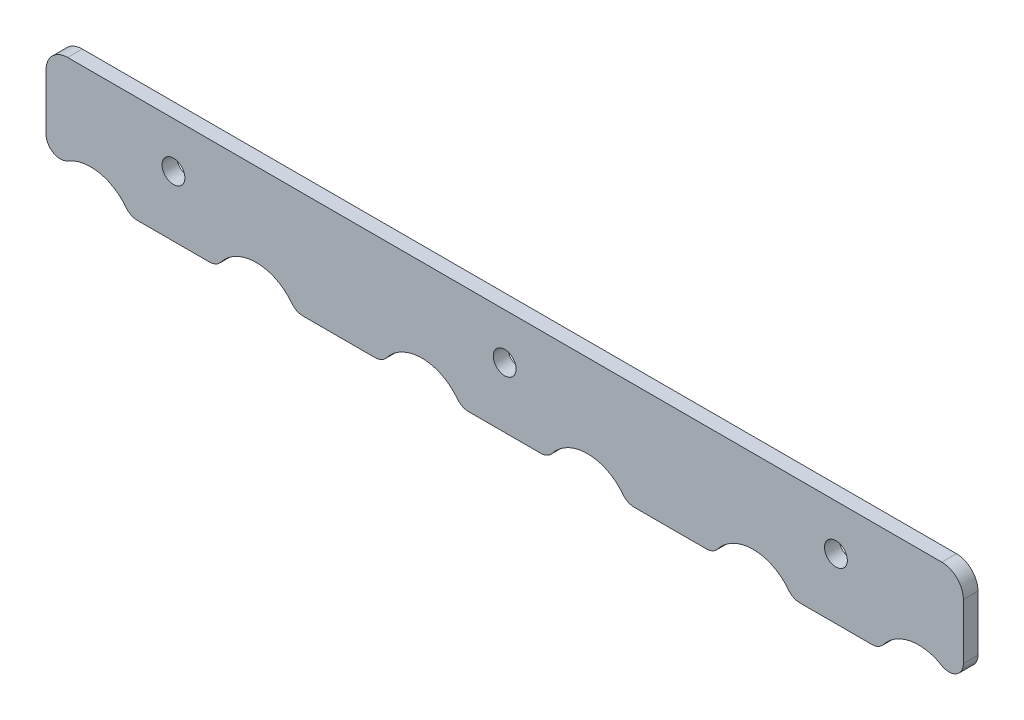
SolidWorks part; units mm, degrees
material "3003-H14"
ref_plane "X-Y Datum" through (0, 0, 0) normal (0, 0, 1) x (1, 0, 0)
ref_plane "X-Z Datum" through (0, 0, 0) normal (0, 1, 0) x (1, 0, 0)
ref_plane "Y-Z Datum" through (0, 0, 0) normal (1, 0, 0) x (0, 0, -1)
sketch "Sketch3" plane through (0, 0, 0) normal (0, 0, 1) x (1, 0, 0)
  line L1 (0, 0) -> (156.4633, 0) construction
  line L2 (0, 0) -> (0, 56.3098) construction
  line L3 (0, 56.3098) -> (156.4633, 56.3098) construction
  line L4 (156.4633, 0) -> (156.4633, 56.3098) construction
  line L5 (4.575, 10.775) -> (4.575, 28.535)
  line L6 (4.575, 28.535) -> (131.975, 28.535)
  line L7 (131.975, 28.535) -> (131.975, 10.775)
  line L9 (4.575, 13.775) -> (131.975, 13.775)
  line L10 (10.775, 10.775) -> (33.775, 10.775) construction
  line L11 (56.775, 10.775) -> (33.775, 10.775) construction
  line L48 (56.775, 10.775) -> (125.775, 10.775) construction
  circle A0 centre (10.775, 10.775) radius 10.775 construction
  circle A1 centre (33.775, 10.775) radius 10.775 construction
  circle A5 centre (56.775, 10.775) radius 10.775 construction
  circle A6 centre (10.775, 10.775) radius 4.7 construction
  circle A7 centre (33.775, 10.775) radius 4.7 construction
  circle A8 centre (56.775, 10.775) radius 4.7 construction
  circle A12 centre (79.775, 10.775) radius 10.775 construction
  circle A13 centre (79.775, 10.775) radius 4.7 construction
  circle A14 centre (102.775, 10.775) radius 10.775 construction
  circle A15 centre (102.775, 10.775) radius 4.7 construction
  circle A16 centre (125.775, 10.775) radius 10.775 construction
  circle A17 centre (125.775, 10.775) radius 4.7 construction
  circle A18 centre (125.775, 10.775) radius 10.775 construction
  circle A19 centre (102.775, 10.775) radius 10.775 construction
  circle A20 centre (79.775, 10.775) radius 10.775 construction
  circle A25 centre (10.775, 10.775) radius 6.2
  circle A26 centre (33.775, 10.775) radius 6.2
  circle A27 centre (56.775, 10.775) radius 6.2
  circle A28 centre (79.775, 10.775) radius 6.2
  circle A29 centre (102.775, 10.775) radius 6.2
  circle A30 centre (125.775, 10.775) radius 6.2
  dimension "D1" = 21.55
  dimension "D9" = 9.4
  dimension "D2" = 23
  dimension "D3" = 1.5
  dimension "D4" = 14.76
  dimension "D8" = 23
  dimension "D11" = 23
  dimension "D5" = 3
  dimension "D10" = 4
  dimension "D7" = 5
extrude "Boss-Extrude1" add sketch "Sketch3" along normal blind 2.032 contours A30 L9 L7 L6 L5 A25 A26 A27 A28 A29 | A25 L9 L5 | A30 L7 L9 region at (4.8045, 13.0347, 0) region at (68.275, 21.6738, 0) region at (131.7455, 13.0347, 0)
fillet "Fillet1" radius 3 2 edges at (4.575, 28.535, 1.016) (131.975, 28.535, 1.016)
fillet "Fillet2" radius 2 12 edges at (131.975, 10.775, 1.016) (120.3491, 13.775, 1.016) (108.2009, 13.775, 1.016) (97.3491, 13.775, 1.016) (85.2009, 13.775, 1.016) (74.3491, 13.775, 1.016) (62.2009, 13.775, 1.016) (51.3491, 13.775, 1.016) (39.2009, 13.775, 1.016) (28.3491, 13.775, 1.016) (16.2009, 13.775, 1.016) (4.575, 10.775, 1.016)
sketch "Sketch4" plane through (0, 0, 0) normal (0, 0, -1) x (-1, 0, 0)
  line L0 (-131.975, 22.185) -> (-4.575, 22.185) construction
  line L1 (-131.975, 25.535) -> (-131.975, 17.8177) construction
  line L2 (-4.575, 17.8177) -> (-4.575, 25.535) construction
  line L3 (-7.575, 28.535) -> (-128.975, 28.535) construction
  line L4 (-68.275, 28.535) -> (-68.275, 13.775) construction
  line L5 (-63.2742, 13.775) -> (-73.2758, 13.775) construction
  line L6 (-68.275, 22.185) -> (-4.575, 22.185) construction
  line L7 (-22.275, 13.775) -> (-22.275, 28.535) construction
  line L8 (-17.2742, 13.775) -> (-27.2758, 13.775) construction
  line L9 (-114.275, 13.775) -> (-114.275, 28.535) construction
  line L10 (-109.2742, 13.775) -> (-119.2758, 13.775) construction
  circle A0 centre (-22.275, 22.185) radius 1.5875
  circle A1 centre (-68.275, 22.185) radius 1.5875
  circle A3 centre (-114.275, 22.185) radius 1.5875
  point P26 (-114.275, 22.185)
  point P27 (-66.7481, 22.185)
  point P28 (-68.275, 22.185)
  point P29 (-64.6957, 22.185)
  point P30 (-68.275, 22.185)
  dimension "D1" = 3.175
  dimension "D2" = 6.35
extrude "Cut-Extrude1" cut sketch "Sketch4" against normal through all
